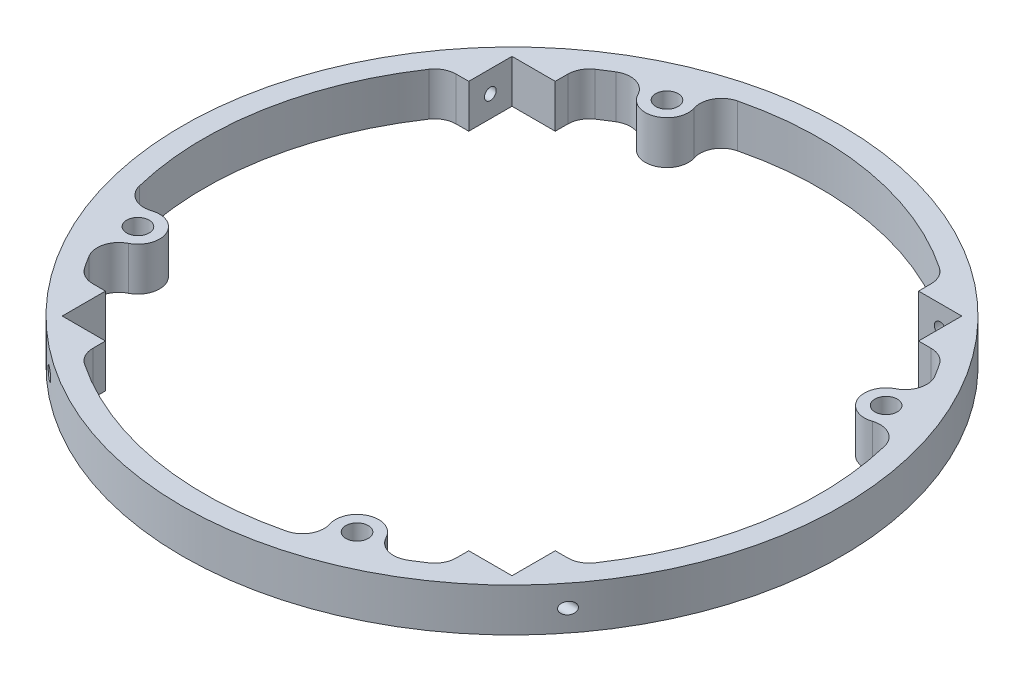
SolidWorks part; units mm, degrees
ref_plane "Front Plane" through (0, 0, 0) normal (0, 0, 1) x (1, 0, 0)
ref_plane "Top Plane" through (0, 0, 0) normal (0, 1, 0) x (1, 0, 0)
ref_plane "Right Plane" through (0, 0, 0) normal (1, 0, 0) x (0, 0, -1)
sketch "Sketch1" plane through (0, 0, 0) normal (0, 1, 0) x (1, 0, 0)
  line L0 (0, 0) -> (0, 84.2831) construction
  line L1 (-52, 52) -> (52, 52) construction
  line L2 (-52, 52) -> (-52, -52) construction
  line L3 (-52, -52) -> (52, -52) construction
  line L4 (52, 52) -> (52, -52) construction
  line L5 (0, 0) -> (-99.9306, 0) construction
  line L6 (0, 0) -> (-52, 52) construction
  line L7 (0, 0) -> (-31.8699, 76.9407) construction
  line L8 (-42, 52) -> (-52, 52)
  line L9 (-52, 52) -> (-52, 42)
  line L10 (-52, 42) -> (-57.493, 42)
  line L11 (-42, 52) -> (-42, 57.493)
  line L12 (-31.7992, 63.7044) -> (-29.953, 59.2474)
  line L13 (-22.5604, 67.5312) -> (-20.7142, 63.0742)
  line L14 (42, 52) -> (42, 57.493)
  line L15 (52, 52) -> (42, 52)
  line L16 (52, 42) -> (52, 52)
  line L17 (52, 42) -> (57.493, 42)
  line L18 (63.7044, 31.7992) -> (59.2474, 29.953)
  line L19 (67.5312, 22.5604) -> (63.0742, 20.7142)
  line L20 (52, -42) -> (57.493, -42)
  line L21 (52, -52) -> (52, -42)
  line L22 (42, -52) -> (52, -52)
  line L23 (42, -52) -> (42, -57.493)
  line L24 (31.7992, -63.7044) -> (29.953, -59.2474)
  line L25 (22.5604, -67.5312) -> (20.7142, -63.0742)
  line L26 (-42, -52) -> (-42, -57.493)
  line L27 (-52, -52) -> (-42, -52)
  line L28 (-52, -42) -> (-52, -52)
  line L29 (-52, -42) -> (-57.493, -42)
  line L30 (-63.7044, -31.7992) -> (-59.2474, -29.953)
  line L31 (-67.5312, -22.5604) -> (-63.0742, -20.7142)
  circle A0 centre (0, 0) radius 76.2
  arc A1 (-57.493, 42) -> (-71.2, 0) centre (0, 0) ccw
  arc A2 (-42, 57.493) -> (-31.7992, 63.7044) centre (0, 0) cw
  arc A3 (-29.953, 59.2474) -> (-20.7142, 63.0742) centre (-25.3336, 61.1608) ccw
  arc A4 (0, 71.2) -> (-22.5604, 67.5312) centre (0, 0) ccw
  arc A5 (42, 57.493) -> (0, 71.2) centre (0, 0) ccw
  arc A6 (57.493, 42) -> (63.7044, 31.7992) centre (0, 0) cw
  arc A7 (59.2474, 29.953) -> (63.0742, 20.7142) centre (61.1608, 25.3336) ccw
  arc A8 (71.2, 0) -> (67.5312, 22.5604) centre (0, 0) ccw
  arc A9 (57.493, -42) -> (71.2, 0) centre (0, 0) ccw
  arc A10 (42, -57.493) -> (31.7992, -63.7044) centre (0, 0) cw
  arc A11 (29.953, -59.2474) -> (20.7142, -63.0742) centre (25.3336, -61.1608) ccw
  arc A12 (0, -71.2) -> (22.5604, -67.5312) centre (0, 0) ccw
  arc A13 (-42, -57.493) -> (0, -71.2) centre (0, 0) ccw
  arc A14 (-57.493, -42) -> (-63.7044, -31.7992) centre (0, 0) cw
  arc A15 (-59.2474, -29.953) -> (-63.0742, -20.7142) centre (-61.1608, -25.3336) ccw
  arc A16 (-71.2, 0) -> (-67.5312, -22.5604) centre (0, 0) ccw
  point P21 (-21.6373, 65.3027)
  point P61 (0, 0)
  dimension "D1" = 152.4
  dimension "D2" = 104
  dimension "D3" = 22.5
  dimension "D4" = 5
  dimension "D5" = 66.2
  dimension "D6" = 10
  dimension "D7" = 10
  dimension "D8" = 4
extrude "Boss-Extrude1" add sketch "Sketch1" along normal blind 10
fillet "Fillet1" radius 5 16 edges at (-67.5312, 5, 22.5604) (-63.7044, 5, 31.7992) (-42, 5, 57.493) (-57.493, 5, 42) (22.5604, 5, 67.5312) (31.7992, 5, 63.7044) (42, 5, 57.493) (57.493, 5, 42) (67.5312, 5, -22.5604) (63.7044, 5, -31.7992) (57.493, 5, -42) (42, 5, -57.493) (-31.7992, 5, -63.7044) (-22.5604, 5, -67.5312) (-42, 5, -57.493) (-57.493, 5, -42)
hole_wizard "#6 (0.204) Diameter Hole1" positions "Sketch4" profile "Sketch3" hole size "#6" standard "ANSI Inch" end condition through all
sketch "Sketch4" plane through (0, 10, 0) normal (0, 1, 0) x (1, 0, 0)
  point P0 (61.1608, 25.3336)
sketch "Sketch3" plane through (61.1608, 10, -25.3336) normal (1, 0, 0) x (0, 0, 1)
  line L0 (0, 0) -> (0, 10)
  line L1 (0, 10) -> (2.5908, 10)
  line L2 (2.5908, 10) -> (2.5908, 0)
  line L5 (2.5908, 0) -> (0, 0)
  line L11 (0, -6.35) -> (0, 107.95) construction
  dimension "Thru Hole Dia." = 5.1816
  dimension "Thru Hole Depth" = 10
hole_wizard "#6-32 Tapped Hole2" positions "Sketch8" profile "Sketch9" tap size "#6-32" standard "ANSI Inch" end condition through all
sketch "Sketch8" plane through (0, 0, -52) normal (0, 0, 1) x (1, 0, 0)
  line L0 (52, 0) -> (42, 10)
  point P0 (47, 5)
  point P9 (0, 0)
  point P10 (47, 5)
sketch "Sketch9" plane through (47, 5, -52) normal (1, 0, 0) x (0, -1, 0)
  line L0 (0, 0) -> (0, 24.2)
  line L1 (0, 24.2) -> (1.3525, 24.2)
  line L2 (1.3525, 24.2) -> (1.3525, 0)
  line L5 (1.3525, 0) -> (0, 0)
  line L11 (0, -6.35) -> (0, 107.95) construction
  dimension "Thru Tap Drill Dia." = 2.7051
  dimension "Thru Tap Drill Depth" = 24.2
cosmetic thread "Hole Thread2" parameters "D2"=3.5052
ref_axis "Axis1" through (0, 10.5, 0) along (0, -1, 0)
pattern_circular "CirPattern1" count 4 over 360 about axis through (0, 10.5, 0) along (0, -1, 0) of "#6 (0.204) Diameter Hole1", "#6-32 Tapped Hole2"
equation "\"TubeDiameter\" = 6.000in"
equation "\"D1@Sketch1\"=\"TubeDiameter\""
equation "\"D5@Sketch1\"=\"TubeDiameter\"/2-10mm"
